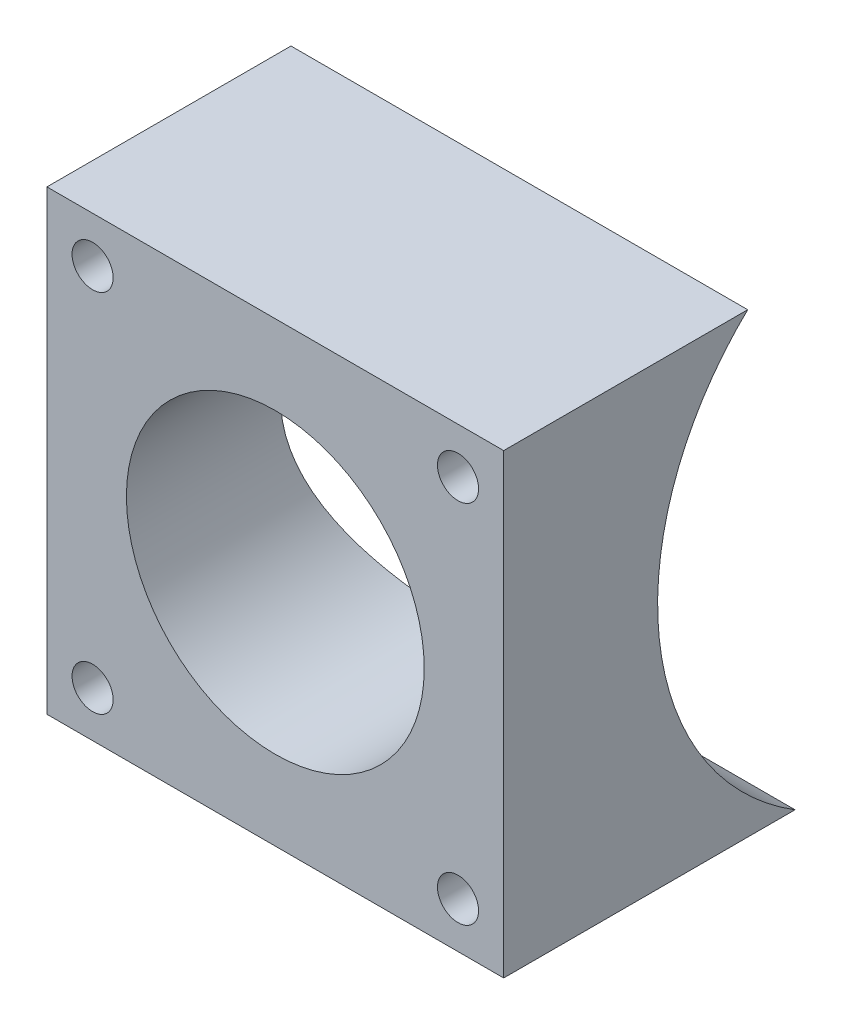
SolidWorks part; units mm, degrees
ref_plane "Front Plane" through (0, 0, 0) normal (0, 0, 1) x (1, 0, 0)
ref_plane "Top Plane" through (0, 0, 0) normal (0, 1, 0) x (1, 0, 0)
ref_plane "Right Plane" through (0, 0, 0) normal (1, 0, 0) x (0, 0, -1)
sketch "Sketch1" plane through (0, 0, 0) normal (0, 0, 1) x (1, 0, 0)
  line L1 (-25, 23) -> (25, 23)
  line L2 (-25, 23) -> (-25, -27)
  line L3 (-25, -27) -> (25, -27)
  line L4 (25, 23) -> (25, -27)
  line L5 (-25, 23) -> (25, -27) construction
  line L6 (-25, -27) -> (25, 23) construction
  circle A0 centre (0, -2) radius 16.3
  circle A1 centre (-20, 18) radius 2.25
  circle A2 centre (20, 18) radius 2.25
  circle A3 centre (20, -22) radius 2.25
  circle A4 centre (-20, -22) radius 2.25
  point P0 (0, -2)
  dimension "D4" = 32.6
  dimension "D6" = 4.5
  dimension "D1" = 2
  dimension "D2" = 50
  dimension "D3" = 50
  dimension "D5" = 20
  dimension "D7" = 20
  dimension "D9" = 20
  dimension "D10" = 20
extrude "Boss-Extrude1" add sketch "Sketch1" along normal blind 48.6
sketch "Sketch2" plane through (0, 0, 0) normal (1, 0, 0) x (0, 0, -1)
  circle A0 centre (0, 0) radius 31.75
  dimension "D1" = 63.5
extrude "Cut-Extrude1" cut sketch "Sketch2" against normal through all and the other way through all
